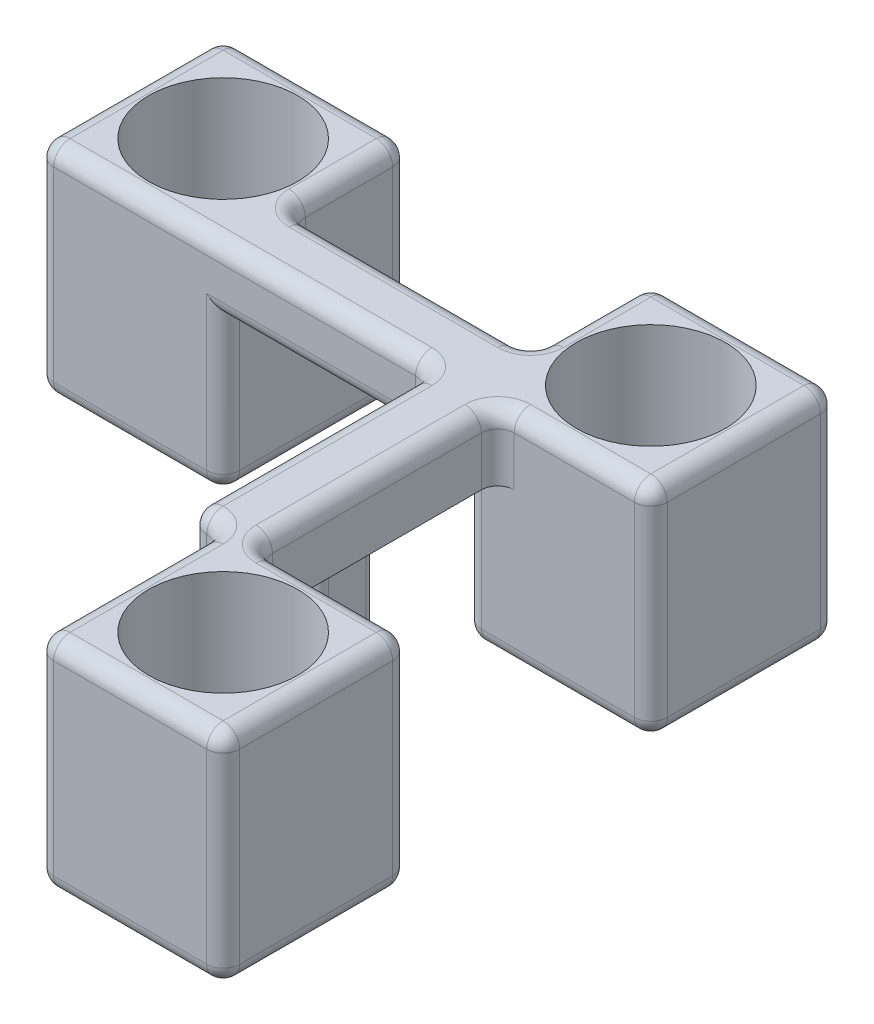
SolidWorks part; units mm, degrees
note: The reader was unsure of these and kept them because the rebuilt part matched: shared geometry of "Sketch1<3>", "Sketch1<4>".
ref_plane "Front Plane" through (0, 0, 0) normal (0, 0, 1) x (1, 0, 0)
ref_plane "Top Plane" through (0, 0, 0) normal (0, 1, 0) x (1, 0, 0)
ref_plane "Right Plane" through (0, 0, 0) normal (1, 0, 0) x (0, 0, -1)
sketch "Sketch1" plane through (0, 0, 0) normal (0, 1, 0) x (1, 0, 0)
  line L0 (-14, 14) -> (14, 14) construction
  line L1 (-14, 14) -> (-14, -14) construction
  line L2 (-14, -14) -> (14, -14) construction
  line L3 (14, 14) -> (14, -14) construction
  line L4 (-14, 14) -> (14, -14) construction
  line L5 (-14, -14) -> (14, 14) construction
  line L6 (4.0147, -0.6147) -> (4.0147, 5.5147)
  line L7 (4.0147, -0.6147) -> (5.0147, -0.6147)
  line L8 (-14, 14) -> (-5.5147, 14)
  line L9 (-14, 14) -> (-14, 5.5147)
  line L10 (-14, 5.5147) -> (-5.5147, 5.5147)
  line L11 (-5.5147, 14) -> (-5.5147, 5.5147)
  line L12 (14, 14) -> (5.5147, 14)
  line L13 (14, 14) -> (14, 5.5147)
  line L14 (14, 5.5147) -> (5.5147, 5.5147)
  line L15 (5.5147, 14) -> (5.5147, 5.5147)
  line L16 (14, -14) -> (5.5147, -14)
  line L17 (14, -14) -> (14, -5.5147)
  line L18 (14, -5.5147) -> (5.5147, -5.5147)
  line L19 (5.5147, -14) -> (5.5147, -5.5147)
  line L20 (4.0147, -0.6147) -> (4.0147, 1.8953)
  line L21 (4.0147, 1.8953) -> (5.0147, 1.8953)
  line L22 (5.0147, -0.6147) -> (5.0147, 1.8953)
  line L23 (4.0147, 5.5147) -> (-5.5147, 5.5147)
  line L24 (-5.5147, 8.5147) -> (5.5147, 8.5147)
  line L25 (4.0147, 1.8953) -> (4.0147, -5.5147)
  line L26 (4.0147, -5.5147) -> (5.5147, -5.5147)
  line L27 (7.0147, 5.5147) -> (7.0147, -5.5147)
  line L28 (-5.5147, 14) -> (-14, 5.5147) construction
  line L29 (-9.7574, 9.7574) -> (9.7574, 9.7574) construction
  line L30 (9.7574, 9.7574) -> (9.7574, -9.7574) construction
  circle A0 centre (-9.7574, 9.7574) radius 3.4
  circle A1 centre (9.7574, 9.7574) radius 3.4
  circle A2 centre (9.7574, -9.7574) radius 3.4
  point P0 (0, 0)
  dimension "D3" = 6.8
  dimension "D1" = 28
  dimension "D2" = 8.4853
  dimension "D4" = 3
  dimension "D5" = 3
  dimension "D6" = 2.51
  dimension "D7" = 7.41
  dimension "D8" = 1.5
  dimension "D9" = 1
extrude "Boss-Extrude1" add sketch "Sketch1" against normal blind 10 contours L11 L8 L9 L10 A0 | L12 L15 L14 L13 A1 | L19 L16 L17 L18 A2
extrude "Boss-Extrude2" add sketch "Sketch1<3>" against normal blind 3 contours L27 L14 L15 L24 L11 L23 L6 L7 L22 L21 L25 L26 L18 | L22 L7 L20 L21
sketch "Sketch1<3>" plane through (0, 0, 0) normal (0, 1, 0) x (1, 0, 0) same geometry as "Sketch1"
extrude "Boss-Extrude3" add sketch "Sketch1<4>" against normal blind 15.67 contours L20 L21 L22 L7
sketch "Sketch1<4>" plane through (0, 0, 0) normal (0, 1, 0) x (1, 0, 0) same geometry as "Sketch1"
fillet "Fillet1" radius 0.75 51 edges at (5.5147, -1.5, 5.5147) (4.0147, -3, 3.0647) (4.0147, -3, -3.705) (4.0147, 0, 0) (4.0147, -1.5, -5.5147) (-0.75, -3, -5.5147) (-5.5147, -6.5, -5.5147) (-4.9926, 0, -5.5147) (9.7574, -10, 5.5147) (5.5147, -10, 9.7574) (9.7574, -10, 13.1574) (-9.7574, -10, -5.5147) (-5.5147, -10, -9.7574) (-9.7574, -10, -6.3574) (5.5147, -10, -9.7574) (9.7574, -10, -5.5147) (9.7574, -10, -6.3574) (5.5147, -5, -14) (9.7574, -10, -14) (9.7574, 0, -14) (14, -5, -14) (14, -10, -9.7574) (14, -5, -5.5147) (14, 0, -9.7574) (14, -5, 5.5147) (14, -10, 9.7574) (14, 0, 9.7574) (14, -5, 14) (9.7574, -10, 14) (5.5147, -5, 14) (9.7574, 0, 14) (-9.7574, -10, -14) (-5.5147, -5, -14) (-9.7574, 0, -14) (-14, -5, -5.5147) (-14, -10, -9.7574) (-14, -5, -14) (-14, 0, -9.7574) (-5.5147, -1.5, -8.5147) (4.0147, -1.5, 5.5147) (5.5147, -1.5, -8.5147) (7.0147, -1.5, -5.5147) (7.0147, -1.5, 5.5147) (-5.5147, 0, -11.2574) (5.5147, 0, -11.2574) (10.5074, 0, -5.5147) (10.5074, 0, 5.5147) (5.5147, -6.5, -5.5147) (0, 0, -8.5147) (5.5147, 0, 9.7574) (7.0147, 0, 0)
fillet "Fillet2" radius 0.4 8 edges at (4.0147, -15.67, -0.6403) (4.5147, -15.67, -1.8953) (5.0147, -15.67, -0.6403) (4.5147, -15.67, 0.6147) (5.0147, -9.335, 0.6147) (4.0147, -8.96, 0.6147) (5.0147, -9.335, -1.8953) (4.0147, -8.96, -1.8953)
ref_plane "Plane1" through (0, -12.17, 0) normal (0, -1, 0) x (-1, 0, 0)
sketch "Sketch3" plane through (0, -12.17, 0) normal (0, -1, 0) x (-1, 0, 0)
  line L0 (-4.5147, -0.2147) -> (-4.5147, 1.4953) construction
  line L1 (-4.6147, -0.2147) -> (-4.4147, -0.2147) construction
  line L2 (-4.4147, 1.4953) -> (-4.6147, 1.4953) construction
  line L3 (-4.0147, 1.4953) -> (-4.0147, -0.2147) construction
  line L4 (-5.5147, -1.1147) -> (-3.5147, -1.1147)
  line L5 (-5.5147, -1.1147) -> (-5.5147, 2.3953)
  line L6 (-5.5147, 2.3953) -> (-3.5147, 2.3953)
  line L7 (-3.5147, -1.1147) -> (-3.5147, 2.3953)
  line L8 (-5.5147, -1.1147) -> (-3.5147, 2.3953) construction
  line L9 (-5.5147, 2.3953) -> (-3.5147, -1.1147) construction
  line L10 (-4.6147, -0.6147) -> (-4.4147, -0.6147) construction
  point P6 (-4.5147, 0.6403)
  dimension "D1" = 0.5
  dimension "D2" = 0.5
extrude "Boss-Extrude4" add sketch "Sketch3" against normal blind 0.5
fillet "Fillet3" radius 0.75 4 edges at (3.5147, -11.92, 1.1147) (3.5147, -11.92, -2.3953) (5.5147, -11.92, -2.3953) (5.5147, -11.92, 1.1147)
